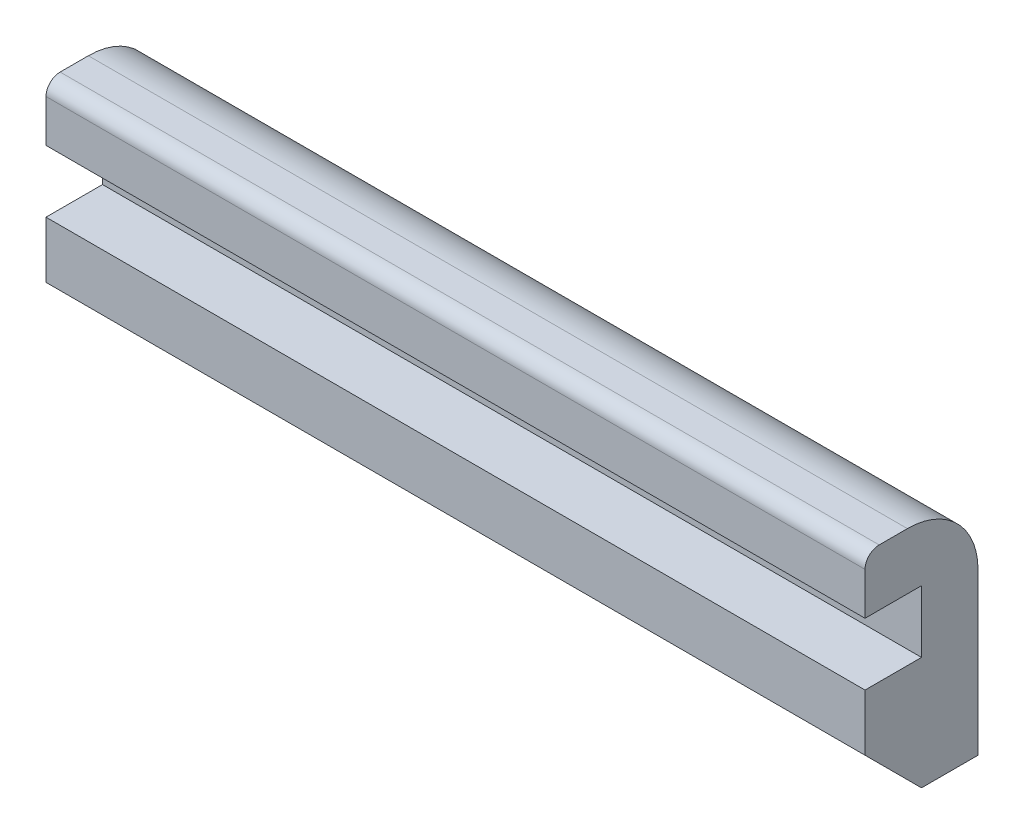
SolidWorks part; units mm, degrees
ref_plane "Front Plane" through (0, 0, 0) normal (0, 0, 1) x (1, 0, 0)
ref_plane "Top Plane" through (0, 0, 0) normal (0, 1, 0) x (1, 0, 0)
ref_plane "Right Plane" through (0, 0, 0) normal (1, 0, 0) x (0, 0, -1)
sketch "Sketch1" plane through (0, 0, 0) normal (0, 1, 0) x (1, 0, 0)
  line L1 (-19.5, 77.5) -> (19.5, 77.5)
  line L2 (-19.5, 77.5) -> (-19.5, -77.5)
  line L3 (-19.5, -77.5) -> (19.5, -77.5)
  line L4 (19.5, 77.5) -> (19.5, -77.5)
  line L5 (-19.5, 77.5) -> (19.5, -77.5) construction
  line L6 (-19.5, -77.5) -> (19.5, 77.5) construction
  point P0 (0, 0)
  dimension "D1" = 39
  dimension "D2" = 155
extrude "Boss-Extrude1" add sketch "Sketch1" along normal blind 2
sketch "Sketch2" plane through (0, 2, 0) normal (0, 1, 0) x (1, 0, 0)
  line L0 (-17.5, -75.5) -> (-17.5, -77.5)
  line L1 (-19.5, 77.5) -> (19.5, 77.5)
  line L2 (-19.5, 77.5) -> (-19.5, -77.5)
  line L3 (-19.5, -77.5) -> (19.5, -77.5)
  line L4 (19.5, 77.5) -> (19.5, -77.5)
  line L5 (-17.5, 75.5) -> (17.5, 75.5)
  line L6 (-17.5, 75.5) -> (-17.5, -75.5)
  line L7 (-17.5, -75.5) -> (17.5, -75.5)
  line L8 (17.5, 75.5) -> (17.5, -75.5)
  line L9 (-17.5, 75.5) -> (17.5, -75.5) construction
  line L10 (-17.5, -75.5) -> (17.5, 75.5) construction
  line L11 (17.5, -75.5) -> (17.5, -77.5)
  point P6 (0, 0)
  line M9 (19.5, -77.5) -> (19.5, 77.5)
  line M10 (19.5, 77.5) -> (-19.5, 77.5)
  line M11 (-19.5, 77.5) -> (-19.5, -77.5)
  line M12 (-19.5, -77.5) -> (19.5, -77.5)
  dimension "D1" = 2
  dimension "D2" = 2
extrude "Boss-Extrude2" add sketch "Sketch2" along normal blind 38 contours L8 L11 L3 L0 L6 L5 M9 M10 M11 M12 region at (-19.0983, 2, 76.5)
sketch "Sketch3" plane through (0, 2, 0) normal (0, 1, 0) x (1, 0, 0)
  line L0 (-17.5, 75.5) -> (-17.5, -77.5) construction
  line L1 (-17.5, -77.5) -> (-15.5, -77.5)
  line L2 (-17.5, -77.5) -> (-17.5, -75.5)
  line L3 (-17.5, -75.5) -> (-15.5, -75.5)
  line L4 (-15.5, -77.5) -> (-15.5, -75.5)
  line L5 (-17.5, -73.3) -> (-15.5, -73.3)
  line L6 (-17.5, -73.3) -> (-17.5, -71.3)
  line L7 (-17.5, -71.3) -> (-15.5, -71.3)
  line L8 (-15.5, -73.3) -> (-15.5, -71.3)
  line L9 (17.5, 75.5) -> (17.5, -77.5) construction
  line L10 (17.5, -77.5) -> (15.5, -77.5)
  line L11 (17.5, -77.5) -> (17.5, -75.5)
  line L12 (17.5, -75.5) -> (15.5, -75.5)
  line L13 (15.5, -77.5) -> (15.5, -75.5)
  line L14 (17.5, -73.3) -> (15.5, -73.3)
  line L15 (17.5, -73.3) -> (17.5, -71.3)
  line L16 (17.5, -71.3) -> (15.5, -71.3)
  line L17 (15.5, -73.3) -> (15.5, -71.3)
  line L18 (15.5, -75.5) -> (15.5, -73.3) construction
  line L19 (-15.5, -73.3) -> (15.5, -73.3) construction
  line L20 (-15.5, -75.5) -> (-15.5, -73.3) construction
  line L21 (-15.5, -75.5) -> (15.5, -75.5) construction
  line L22 (15.5, -71.3) -> (-15.5, -71.3) construction
  dimension "D1" = 2
  dimension "D2" = 2
  dimension "D3" = 2.2
  dimension "D4" = 2
extrude "Boss-Extrude3" add sketch "Sketch3" along normal up to surface (38 mm away) up to face at (0, 40, 0.5)
sketch "Sketch4" plane through (0, 0, -75.5) normal (0, 0, 1) x (1, 0, 0)
  line L0 (-17.5, 40) -> (-15.5, 40)
  line L1 (-17.5, 40) -> (17.5, 40) construction
  line L2 (-15.5, 40) -> (-15.5, 38)
  line L3 (-15.5, 38) -> (-17.5, 38)
  line L5 (-17.5, 38) -> (-17.5, 40)
  line L7 (-17.5, 40) -> (-17.5, 2) construction
  line L8 (-15.5, 33.8) -> (-17.5, 31.8)
  line L9 (-17.5, 31.8) -> (-17.5, 35.8)
  line L10 (-15.5, 33.8) -> (-15.5, 35.8)
  line L11 (-15.5, 35.8) -> (-17.5, 35.8)
  line L12 (0, 0) -> (0, 40) construction
  line L13 (15.5, 35.8) -> (17.5, 35.8)
  line L14 (15.5, 33.8) -> (15.5, 35.8)
  line L15 (17.5, 31.8) -> (17.5, 35.8)
  line L16 (15.5, 33.8) -> (17.5, 31.8)
  line L17 (17.5, 38) -> (17.5, 40)
  line L18 (15.5, 38) -> (17.5, 38)
  line L19 (15.5, 40) -> (15.5, 38)
  line L20 (17.5, 40) -> (15.5, 40)
  dimension "D1" = 2
  dimension "D2" = 2
  dimension "D3" = 45
  dimension "D4" = 2.2
  dimension "D5" = 2
extrude "Boss-Extrude4" add sketch "Sketch4" along normal up to surface (153 mm away) up to face at (0, 20.5, 77.5)
sketch "Sketch5" plane through (0, 2, 0) normal (0, 1, 0) x (1, 0, 0)
  line L1 (-15.5, -77.5) -> (15.5, -77.5)
  line L2 (-15.5, -77.5) -> (-15.5, -75.5)
  line L3 (-15.5, -75.5) -> (15.5, -75.5)
  line L4 (15.5, -77.5) -> (15.5, -75.5)
  line L5 (-15.5, -71.3) -> (15.5, -71.3)
  line L6 (-15.5, -71.3) -> (-15.5, -73.3)
  line L7 (-15.5, -73.3) -> (15.5, -73.3)
  line L8 (15.5, -71.3) -> (15.5, -73.3)
sketch "Sketch6" plane through (0, 0, -75.5) normal (0, 0, 1) x (1, 0, 0)
  line L0 (-17.5, 38) -> (-15.5, 38) construction
  line L1 (-17.5, 38) -> (17.5, 38)
  line L2 (-17.5, 38) -> (-17.5, 35.8)
  line L3 (-17.5, 35.8) -> (17.5, 35.8)
  line L4 (17.5, 38) -> (17.5, 35.8)
  line L5 (-17.5, 38) -> (-17.5, 35.8) construction
  line L6 (-15.5, 35.8) -> (-17.5, 35.8) construction
extrude "Cut-Extrude1" cut sketch "Sketch6" along normal through all
sketch "Sketch7" plane through (0, 2, 0) normal (0, 1, 0) x (1, 0, 0)
  line L1 (-17.5, -75.5) -> (17.5, -75.5)
  line L2 (-17.5, -75.5) -> (-17.5, -73.3)
  line L3 (-17.5, -73.3) -> (17.5, -73.3)
  line L4 (17.5, -75.5) -> (17.5, -73.3)
extrude "Cut-Extrude2" cut sketch "Sketch7" along normal through all
extrude "Boss-Extrude5" add sketch "Sketch5" along normal blind 2
sketch "Sketch8" plane through (0, 0, 0) normal (1, 0, 0) x (0, 0, -1)
  line L0 (75.5, 40) -> (73.5, 40)
  line L1 (-73.3, 40) -> (75.5, 40) construction
  line L2 (73.5, 40) -> (73.5, 38)
  line L3 (-73.3, 38) -> (75.5, 38) construction
  line L4 (73.5, 38) -> (75.5, 38)
  line L5 (75.5, 38) -> (75.5, 40)
  line L6 (75.5, 35.8) -> (73.5, 35.8)
  line L7 (-73.3, 35.8) -> (75.5, 35.8) construction
  line L8 (73.5, 35.8) -> (73.5, 33.8)
  line L9 (-71.3, 33.8) -> (75.5, 33.8) construction
  line L10 (73.5, 33.8) -> (75.5, 31.8)
  line L11 (75.5, 31.8) -> (75.5, 35.8)
  dimension "D1" = 2
extrude "Boss-Extrude6" add sketch "Sketch8" along normal up to surface and the other way up to surface up to face at (17.5, 16.9, -2.1) other way up to face at (-17.5, 16.9, -2.1)
sketch "Sketch10" plane through (-17.5, 0, 0) normal (1, 0, 0) x (0, 0, -1)
  line L1 (-75.5, 35.8) -> (-77.5, 35.8)
  line L2 (-75.5, 35.8) -> (-75.5, 38)
  line L3 (-75.5, 38) -> (-77.5, 38)
  line L4 (-77.5, 35.8) -> (-77.5, 38)
  line L5 (-73.3, 40) -> (-75.5, 40)
  line L6 (-73.3, 40) -> (-73.3, 38)
  line L7 (-73.3, 38) -> (-75.5, 38)
  line L8 (-75.5, 40) -> (-75.5, 38)
  line M1 (-75.5, 40) -> (-75.5, 38)
  line M2 (-75.5, 38) -> (-77.5, 38)
  line M3 (-77.5, 38) -> (-77.5, 35.8)
  line M4 (-77.5, 35.8) -> (-75.5, 35.8)
  line M11 (-73.3, 38) -> (-73.3, 40)
  line M12 (-73.3, 40) -> (-75.5, 40)
extrude "Boss-Extrude8" add sketch "Sketch10" along normal up to surface (2 mm away) contours L2 M4 M2 M3 | L7 M11 M12 M1 region at (-17.5, 39, 74.4) region at (-17.5, 36.9, 76.5) up to face at (-15.5, 39, -0.1)
sketch "Sketch11" plane through (17.5, 0, 0) normal (-1, 0, 0) x (0, 0, 1)
  line L1 (75.5, 35.8) -> (77.5, 35.8)
  line L2 (75.5, 35.8) -> (75.5, 38)
  line L3 (75.5, 38) -> (77.5, 38)
  line L4 (77.5, 35.8) -> (77.5, 38)
  line L5 (73.3, 40) -> (75.5, 40)
  line L6 (73.3, 40) -> (73.3, 38)
  line L7 (73.3, 38) -> (75.5, 38)
  line L8 (75.5, 40) -> (75.5, 38)
  line M2 (75.5, 35.8) -> (77.5, 35.8)
  line M3 (77.5, 35.8) -> (77.5, 38)
  line M4 (77.5, 38) -> (75.5, 38)
  line M5 (75.5, 38) -> (75.5, 40)
  line M6 (75.5, 40) -> (73.3, 40)
  line M7 (73.3, 40) -> (73.3, 38)
extrude "Boss-Extrude9" add sketch "Sketch11" along normal up to surface (2 mm away) contours L2 M2 M3 M4 | L7 M7 M5 M6 region at (17.5, 36.9, 76.5) region at (17.5, 39, 74.4) up to face at (15.5, 39, -0.1)
fillet "Fillet2" radius 2.5 17 edges at (-17.5, 16.9, 71.3) (17.5, 16.9, 71.3) (19.5, 20, 77.5) (-19.5, 20, 77.5) (-19.5, 20, -77.5) (-17.5, 16.9, -75.5) (17.5, 16.9, -75.5) (19.5, 20, -77.5) (-19.5, 40, 0) (0, 40, -77.5) (19.5, 40, 0) (0, 0, -77.5) (0, 0, 77.5) (-19.5, 0, 0) (19.5, 0, 0) (-17.5, 40, 77.5) (17.5, 40, 77.5)
sketch "Sketch13" plane through (0, 0, -77.5) normal (0, 0, -1) x (-1, 0, 0)
  line L0 (15.5, 37.5) -> (15.5, 4) construction
  line L1 (-15.5, 7) -> (15.5, 7)
  line L2 (-15.5, 7) -> (-15.5, 4)
  line L3 (-15.5, 4) -> (15.5, 4)
  line L4 (15.5, 7) -> (15.5, 4)
  dimension "D1" = 3
sketch "Sketch14" plane through (0, 0, -75.5) normal (0, 0, 1) x (1, 0, 0)
  line L1 (-18.25, 9) -> (18.25, 9)
  line L2 (-18.25, 9) -> (-18.25, 1.25)
  line L3 (-18.25, 1.25) -> (18.25, 1.25)
  line L4 (18.25, 9) -> (18.25, 1.25)
  line L5 (15.5, 7) -> (-15.5, 7) construction
  line L7 (17, 0) -> (17, 2.5) construction
  line L8 (19.5, 2.5) -> (17, 2.5) construction
  line L10 (-19.5, 2.5) -> (-17, 2.5) construction
  point P20 (17, 1.25)
  point P23 (18.25, 2.5)
  point P26 (-18.25, 2.5)
  dimension "D1" = 2
extrude "Boss-Extrude10" add sketch "Sketch14" along normal blind 2
extrude "Cut-Extrude4" cut sketch "Sketch13" against normal blind 2
fillet "Fillet3" radius 2 1 edges at (0, 9, -73.5)
fillet "Fillet4" radius 0.5 12 edges at (0, 4, -77.5) (0, 7, -77.5) (15.5, 7, -76.5) (15.5, 4, -76.5) (15.5, 5.5, -77.5) (-15.5, 4, -76.5) (-15.5, 7, -76.5) (-15.5, 5.5, -77.5) (0, 7, -75.5) (-15.5, 5.5, -75.5) (0, 4, -75.5) (15.5, 5.5, -75.5)
sketch "Sketch15" plane through (0, 0, 0) normal (0, -1, 0) x (1, 0, 0)
  line L0 (0, 77.5) -> (0, 0) construction
  line L1 (-17, 77.5) -> (17, 77.5) construction
  line L2 (0, 0) -> (0, -77.5) construction
  line L4 (17, -77.5) -> (-17, -77.5) construction
  circle A0 centre (0, 38.75) radius 5.1
  circle A1 centre (0, -38.75) radius 5.1
  dimension "D1" = 10.2
extrude "Cut-Extrude5" cut sketch "Sketch15" against normal through all
sketch "Sketch16" plane through (0, 2, 0) normal (0, 1, 0) x (1, 0, 0)
  circle A0 centre (0, 38.75) radius 7.1
  circle A1 centre (0, -38.75) radius 7.1
  circle A2 centre (0, 38.75) radius 5.1 construction
  dimension "D1" = 2
extrude "Boss-Extrude11" add sketch "Sketch16" along normal blind 1
fillet "Fillet5" radius 0.5 4 edges at (0, 2, 45.85) (0, 2, -31.65) (0, 3, 45.85) (0, 3, -31.65)
sketch "Sketch12" plane through (0, 0, -75.5) normal (0, 0, 1) x (1, 0, 0)
  line L0 (0, 0) -> (0, 40) construction
  line L1 (15.5, 40) -> (-15.5, 40) construction
  line L2 (0, 20) -> (-10, 20)
  line L3 (0, 20) -> (-9.0097, 15.6612)
  line L4 (0, 20) -> (-6.2349, 12.1817)
  line L5 (0, 20) -> (-2.2252, 10.2507)
  line L6 (0, 20) -> (2.2252, 10.2507)
  line L7 (0, 20) -> (6.2349, 12.1817)
  line L8 (0, 20) -> (9.0097, 15.6612)
  line L9 (0, 20) -> (10, 20)
  line L10 (0, 20) -> (9.0097, 24.3388)
  line L11 (0, 20) -> (6.2349, 27.8183)
  line L12 (0, 20) -> (2.2252, 29.7493)
  line L13 (0, 20) -> (-2.2252, 29.7493)
  line L14 (0, 20) -> (-6.2349, 27.8183)
  line L15 (0, 20) -> (-9.0097, 24.3388)
  circle A0 centre (0, 20) radius 10
  circle A1 centre (0, 20) radius 7.5
  circle A2 centre (0, 20) radius 5
  circle A3 centre (0, 20) radius 2.5
  point P26 (0, 20)
  dimension "D1" = 20
  dimension "D2" = 2.5
  dimension "D3" = 2.5
  dimension "D4" = 2.5
  dimension "D5" = 14
extrude "Cut-Extrude3" cut sketch "Sketch12" against normal through all contours A1 L6 A0 L7 | A1 L4 A0 L5 | A1 L2 A0 L3 | A1 L14 A0 L15 | A1 L0 A0 L13 | L0 A1 L12 A0 | A1 L10 A0 L11 | A1 L8 A0 L9 | A3 L8 A2 L9 | A3 L10 A2 L11 | L0 A3 L12 A2 | A3 L0 A2 L13 | A3 L14 A2 L15 | A3 L2 A2 L3 | A3 L4 A2 L5 | A3 L6 A2 L7 region at (-3.7903, 12.1293, -75.5) region at (3.7903, 12.1293, -75.5) region at (-1.6732, 16.5256, -75.5) region at (1.6732, 16.5256, -75.5) region at (-8.5168, 18.0561, -75.5) region at (8.5168, 18.0561, -75.5) region at (-0.4345, 23.8563, -75.5) region at (0.4345, 23.8563, -75.5) region at (-3.7596, 19.1419, -75.5) region at (3.7596, 19.1419, -75.5) region at (3.015, 22.4044, -75.5) region at (-3.015, 22.4044, -75.5) region at (-6.8299, 25.4467, -75.5) region at (6.8299, 25.4467, -75.5) region at (-0.9843, 28.7358, -75.5) region at (0.9843, 28.7358, -75.5)
fillet "Fillet6" radius 0.4 112 edges at (5.4555, 26.841, -77.5) (7.8183, 26.2349, -77.5) (7.8835, 23.7965, -77.5) (5.8637, 24.6762, -77.5) (3.75, 20, -77.5) (4.8746, 18.8874, -77.5) (3.3786, 18.3729, -77.5) (2.4373, 19.4437, -77.5) (-1.9471, 28.5306, -77.5) (0, 30, -77.5) (1.9471, 28.5306, -77.5) (0, 27.5, -77.5) (-7.8835, 16.2035, -77.5) (-9.7493, 17.7748, -77.5) (-8.75, 20, -77.5) (-7.312, 18.3311, -77.5) (2.3381, 17.0681, -77.5) (2.1694, 15.4952, -77.5) (0.8345, 16.344, -77.5) (1.0847, 17.7476, -77.5) (-0.8345, 16.344, -77.5) (-2.1694, 15.4952, -77.5) (-2.3381, 17.0681, -77.5) (-1.0847, 17.7476, -77.5) (5.4555, 13.159, -77.5) (4.3388, 10.9903, -77.5) (1.9471, 11.4694, -77.5) (3.2541, 13.2427, -77.5) (0, 22.5, -77.5) (-0.8345, 23.656, -77.5) (0, 25, -77.5) (0.8345, 23.656, -77.5) (-3.3786, 21.6271, -77.5) (-3.9092, 23.1174, -77.5) (-2.3381, 22.9319, -77.5) (-1.9546, 21.5587, -77.5) (-3.3786, 18.3729, -77.5) (-4.8746, 18.8874, -77.5) (-3.75, 20, -77.5) (-2.4373, 19.4437, -77.5) (-1.9471, 11.4694, -77.5) (-4.3388, 10.9903, -77.5) (-5.4555, 13.159, -77.5) (-3.2541, 13.2427, -77.5) (-7.8835, 23.7965, -77.5) (-7.8183, 26.2349, -77.5) (-5.4555, 26.841, -77.5) (-5.8637, 24.6762, -77.5) (2.3381, 22.9319, -77.5) (3.9092, 23.1174, -77.5) (3.3786, 21.6271, -77.5) (1.9546, 21.5587, -77.5) (8.75, 20, -77.5) (9.7493, 17.7748, -77.5) (7.8835, 16.2035, -77.5) (7.312, 18.3311, -77.5) (7.8835, 23.7965, -75.5) (7.8183, 26.2349, -75.5) (5.4555, 26.841, -75.5) (5.8637, 24.6762, -75.5) (3.3786, 18.3729, -75.5) (4.8746, 18.8874, -75.5) (3.75, 20, -75.5) (2.4373, 19.4437, -75.5) (1.9471, 28.5306, -75.5) (0, 30, -75.5) (-1.9471, 28.5306, -75.5) (0, 27.5, -75.5) (-8.75, 20, -75.5) (-9.7493, 17.7748, -75.5) (-7.8835, 16.2035, -75.5) (-7.312, 18.3311, -75.5) (0.8345, 16.344, -75.5) (2.1694, 15.4952, -75.5) (2.3381, 17.0681, -75.5) (1.0847, 17.7476, -75.5) (-2.3381, 17.0681, -75.5) (-2.1694, 15.4952, -75.5) (-0.8345, 16.344, -75.5) (-1.0847, 17.7476, -75.5) (1.9471, 11.4694, -75.5) (4.3388, 10.9903, -75.5) (5.4555, 13.159, -75.5) (3.2541, 13.2427, -75.5) (0, 22.5, -75.5) (0.8345, 23.656, -75.5) (0, 25, -75.5) (-0.8345, 23.656, -75.5) (-2.3381, 22.9319, -75.5) (-3.9092, 23.1174, -75.5) (-3.3786, 21.6271, -75.5) (-1.9546, 21.5587, -75.5) (-3.75, 20, -75.5) (-4.8746, 18.8874, -75.5) (-3.3786, 18.3729, -75.5) (-2.4373, 19.4437, -75.5) (-5.4555, 13.159, -75.5) (-4.3388, 10.9903, -75.5) (-1.9471, 11.4694, -75.5) (-3.2541, 13.2427, -75.5) (-5.4555, 26.841, -75.5) (-7.8183, 26.2349, -75.5) (-7.8835, 23.7965, -75.5) (-5.8637, 24.6762, -75.5) (3.3786, 21.6271, -75.5) (3.9092, 23.1174, -75.5) (2.3381, 22.9319, -75.5) (7.8835, 16.2035, -75.5) (9.7493, 17.7748, -75.5) (8.75, 20, -75.5) (7.312, 18.3311, -75.5) (1.9546, 21.5587, -75.5)
fillet "Fillet7" radius 0.5 8 edges at (15.5, 40, 0.75) (15.5, 39.2678, 76.7678) (-15.5, 40, 0.75) (-15.5, 39.2678, 76.7678) (0, 40, -73.5) (15.5, 20.75, 77.5) (-15.5, 20.75, 77.5) (0, 4, 77.5)
sketch "Sketch17" plane through (0, 0, 0) normal (0, -1, 0) x (1, 0, 0)
  line L0 (-17, -77.5) -> (-17, 70.3)
  line L1 (-17, -77.5) -> (17, -77.5)
  line L2 (17, -77.5) -> (17, 70.3)
  line L3 (17, -75) -> (17, 75) construction
  line L5 (17, 70.3) -> (15, 71.3)
  line L6 (15, 71.3) -> (15, 77.5)
  line L7 (15, 77.5) -> (-15, 77.5)
  line L8 (-15, 77.5) -> (-15, 71.3)
  line L9 (-15, 71.3) -> (-17, 70.3)
  line L10 (-17, 75) -> (-17, -75) construction
  line L12 (-15, 71.3) -> (15, 71.3) construction
  line L13 (17, 70.3) -> (-17, 70.3) construction
  line L14 (0, 71.3) -> (0, 77.5) construction
  line L15 (-17, 77.5) -> (17, 77.5) construction
  arc A0 (-19.5, -75) -> (-17, -77.5) centre (-17, -75) ccw construction
  dimension "D1" = 1
  dimension "D2" = 30
  dimension "D3" = 6.2
extrude "Cut-Extrude6" cut sketch "Sketch17" against normal blind 6
sketch "Sketch18" plane through (0, 0, 0) normal (0, 0, 1) x (1, 0, 0)
  line L0 (15, 9) -> (-15, 9) construction
  line L1 (-14.5, 9) -> (14.5, 9)
  line L2 (-14.5, 9) -> (-14.5, 6)
  line L3 (-14.5, 6) -> (14.5, 6)
  line L4 (14.5, 9) -> (14.5, 6)
  line L5 (-17, 6) -> (17, 6) construction
  line L6 (0, 6) -> (0, 0) construction
  dimension "D1" = 29
extrude "Cut-Extrude8" cut sketch "Sketch18" against normal through all
sketch "Sketch20" plane through (0, 0, 0) normal (0, 0, 1) x (1, 0, 0)
  line L0 (-16, 40) -> (16, 40) construction
  line L1 (-19.5, 40) -> (-14.5, 40)
  line L2 (-19.5, 40) -> (-19.5, 0)
  line L3 (-19.5, 0) -> (-14.5, 0)
  line L4 (-14.5, 40) -> (-14.5, 0)
  line L5 (-14.5, 6) -> (14.5, 6)
  line L6 (-14.5, 6) -> (-14.5, 40)
  line L7 (-14.5, 40) -> (14.5, 40)
  line L8 (14.5, 6) -> (14.5, 40)
  line L9 (14.5, 40) -> (19.5, 40)
  line L10 (14.5, 40) -> (14.5, 0)
  line L11 (14.5, 0) -> (19.5, 0)
  line L12 (19.5, 40) -> (19.5, 0)
  line L13 (-15, 0) -> (-17, 0) construction
  line L14 (-19.5, 2.5) -> (-19.5, 37.5) construction
  line L15 (17, 0) -> (15, 0) construction
  line L16 (19.5, 37.5) -> (19.5, 2.5) construction
extrude "Cut-Extrude11" cut sketch "Sketch20" against normal through all both and the other way through all contours L12 L9 L8 L10 L11 | L1 L2 L3 L4 region at (17, 20, 0)
sketch "Sketch21" plane through (0, 0, -75.5) normal (0, 0, 1) x (1, 0, 0)
  line L1 (-14.5, 31.8) -> (14.5, 31.8)
  line L2 (-14.5, 31.8) -> (-14.5, 40)
  line L3 (-14.5, 40) -> (14.5, 40)
  line L4 (14.5, 31.8) -> (14.5, 40)
  line L5 (14.5, 31.8) -> (-14.5, 31.8)
  line L6 (14.5, 31.8) -> (14.5, 9)
  line L7 (14.5, 9) -> (-14.5, 9)
  line L8 (-14.5, 31.8) -> (-14.5, 9)
extrude "Cut-Extrude12" cut sketch "Sketch21" against normal through all contours L1 L8 L7 L6 region at (0, 20.4, -75.5)
